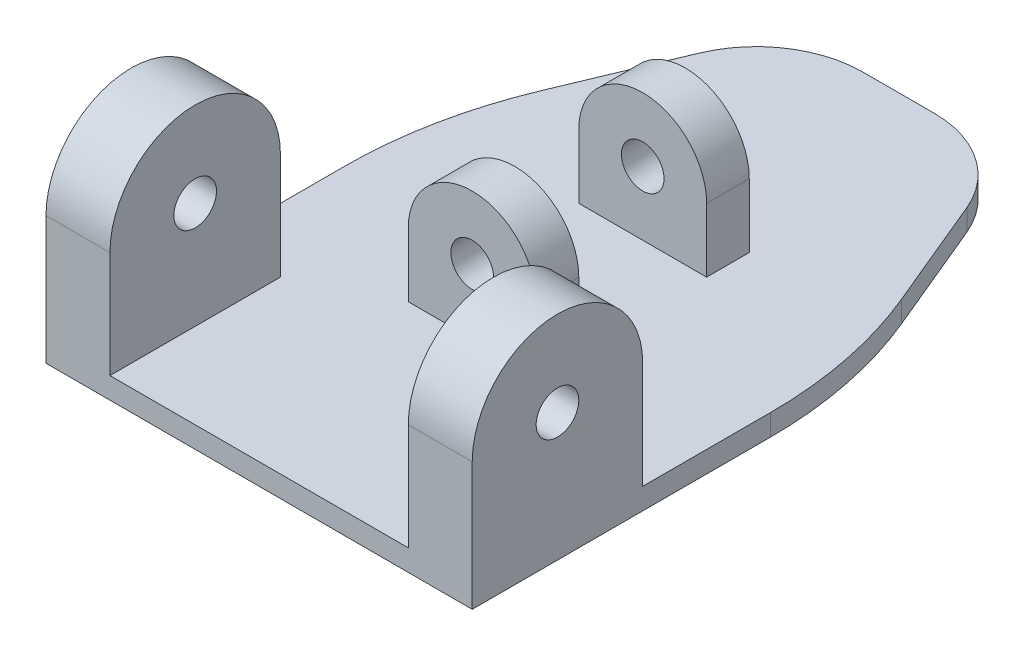
SolidWorks part; units mm, degrees
ref_plane "前视基准面" through (0, 0, 0) normal (0, 0, 1) x (1, 0, 0)
ref_plane "上视基准面" through (0, 0, 0) normal (0, 1, 0) x (1, 0, 0)
ref_plane "右视基准面" through (0, 0, 0) normal (1, 0, 0) x (0, 0, -1)
other "Configuration Table"
sketch "草图1" plane through (0, 0, 0) normal (0, 1, 0) x (1, 0, 0)
  line L0 (0, 0) -> (0, 255.8207) construction
  line L1 (-100, 0) -> (100, 0)
  line L2 (100, 0) -> (100, 180)
  line L3 (100, 180) -> (50, 300)
  line L4 (50, 300) -> (-50, 300)
  line L5 (-100, 180) -> (-50, 300)
  line L6 (-100, 0) -> (-100, 180)
  point P8 (0, 300)
  dimension "D1" = 300
  dimension "D2" = 100
  dimension "D3" = 120
  dimension "D4" = 50
extrude "凸台-拉伸1" add sketch "草图1" along normal blind 10
sketch "草图2" plane through (100, 0, 0) normal (1, 0, 0) x (0, 0, -1)
  line L0 (40, 100) -> (40, -10.3339) construction
  line L1 (0, 10) -> (0, 0) construction
  line L2 (0, 10) -> (0, 60)
  line L3 (80, 10) -> (80, 60)
  arc A0 (80, 60) -> (0, 60) centre (40, 60) ccw
  circle A1 centre (40, 60) radius 10
  line M6 (180, 10) -> (0, 10)
  dimension "D3" = 20
  dimension "D1" = 40
  dimension "D2" = 50
extrude "凸台-拉伸2" add sketch "草图2" against normal up to surface (200 mm away) contours A0 L0 A1 L3 M6 | L0 A0 L2 A1 M6 region at (100, 50.7514, -59.5727) region at (100, 50.7514, -20.4273) up to face at (-100, 5, -90)
sketch "草图3" plane through (0, 10, 0) normal (0, 1, 0) x (1, 0, 0)
  line L0 (0, 0) -> (0, 135.8056) construction
  line L1 (-100, 0) -> (100, 0) construction
  line L2 (-70, 0) -> (70, 0)
  line L3 (-70, 0) -> (-70, 100)
  line L4 (-70, 100) -> (70, 100)
  line L5 (70, 0) -> (70, 100)
  line L6 (100, 0) -> (100, 80) construction
  line L7 (-100, 80) -> (-100, 0) construction
  dimension "D1" = 30
  dimension "D2" = 30
  dimension "D3" = 100
extrude "切除-拉伸1" cut sketch "草图3" along normal blind 171
sketch "草图4" plane through (0, 0, 0) normal (0, 0, 1) x (1, 0, 0)
  line L0 (0, 0) -> (0, 92.3322) construction
  line L1 (30, 40) -> (30, 10)
  line L2 (-30, 40) -> (-30, 10)
  line L3 (-70, 10) -> (70, 10) construction
  arc A0 (-30, 40) -> (30, 40) centre (0, 40) cw
  circle A1 centre (0, 40) radius 10
  line M10 (70, 10) -> (-70, 10)
  dimension "D2" = 30
  dimension "D3" = 20
  dimension "D1" = 30
extrude "凸台-拉伸3" add sketch "草图4" against normal blind 100 from offset 100 contours L0 L1 A0 A1 M10 | L0 A1 A0 L2 M10 region at (-15.0598, 36.8961, 0) region at (15.0598, 36.8961, 0) offset against normal yes
sketch "草图5" plane through (0, 10, 0) normal (0, 1, 0) x (1, 0, 0)
  line L0 (-47.074, 150) -> (51.1394, 150) construction
  line L1 (30, 200) -> (-30, 200) construction
  line L2 (30, 100) -> (-30, 100) construction
  line L3 (-30, 100) -> (30, 100) construction
  line L4 (-40, 180) -> (40, 180)
  line L5 (-40, 180) -> (-40, 120)
  line L6 (-40, 120) -> (40, 120)
  line L7 (40, 180) -> (40, 120)
  line L8 (30, 200) -> (30, 100) construction
  line L9 (-30, 200) -> (-30, 100) construction
  dimension "D1" = 20
  dimension "D2" = 20
  dimension "D3" = 10
  dimension "D4" = 10
extrude "切除-拉伸2" cut sketch "草图5" along normal blind 110 contours L7 L6 L5 L4
fillet "圆角1" radius 50 2 edges at (-50, 5, -300) (50, 5, -300)
fillet "圆角2" radius 200 2 edges at (-100, 5, -180) (100, 5, -180)
